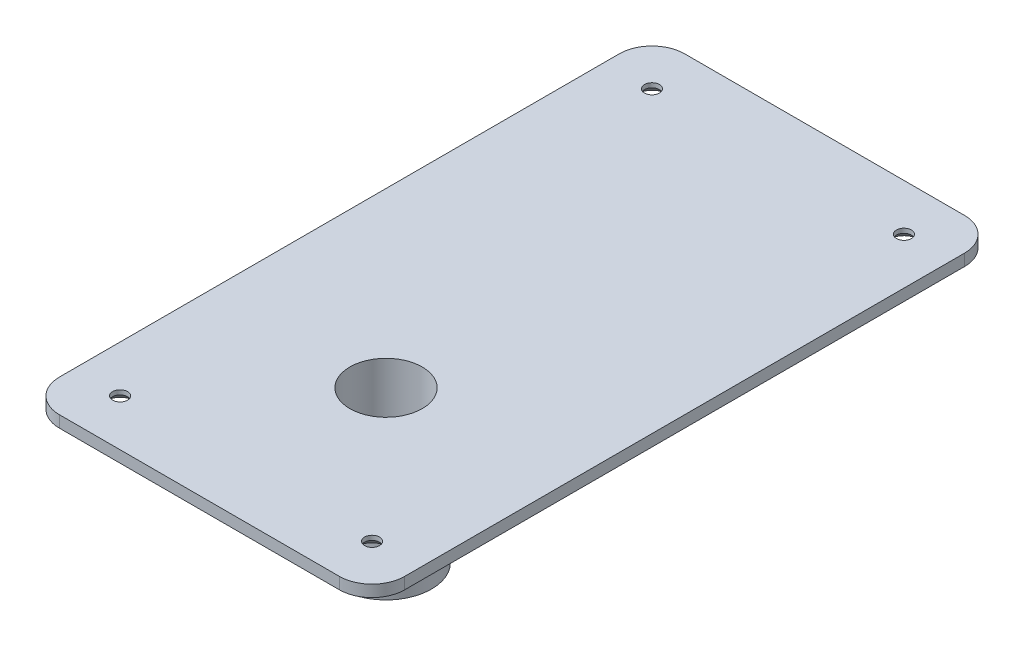
SolidWorks part; units mm, degrees
ref_plane "Front Plane" through (0, 0, 0) normal (0, 0, 1) x (1, 0, 0)
ref_plane "Top Plane" through (0, 0, 0) normal (0, 1, 0) x (1, 0, 0)
ref_plane "Right Plane" through (0, 0, 0) normal (1, 0, 0) x (0, 0, -1)
sketch "Sketch1" plane through (0, 0, 0) normal (0, 1, 0) x (1, 0, 0)
  line L0 (-37, 60) -> (-37, -60)
  line L1 (-30, 70) -> (30, 70)
  line L2 (-40, 60) -> (-40, -60)
  line L3 (-30, -70) -> (30, -70)
  line L4 (40, 60) -> (40, -60)
  line L5 (-40, 70) -> (40, -70) construction
  line L6 (-40, -70) -> (40, 70) construction
  line L7 (-30, -67) -> (30, -67)
  line L8 (37, 60) -> (37, -60)
  line L9 (-30, 67) -> (30, 67)
  line L10 (0, 70) -> (0, -70) construction
  line L11 (40, 0) -> (-40, 0) construction
  arc A0 (-40, -60) -> (-30, -70) centre (-30, -60) ccw
  arc A1 (30, -70) -> (40, -60) centre (30, -60) ccw
  arc A2 (30, 70) -> (40, 60) centre (30, 60) cw
  arc A3 (-30, 70) -> (-40, 60) centre (-30, 60) ccw
  arc A4 (-37, -60) -> (-30, -67) centre (-30, -60) ccw
  arc A5 (30, -67) -> (37, -60) centre (30, -60) ccw
  arc A6 (30, 67) -> (37, 60) centre (30, 60) cw
  arc A7 (-30, 67) -> (-37, 60) centre (-30, 60) ccw
  circle A8 centre (0, -27) radius 7.75
  circle A9 centre (0, -27) radius 9.75
  point P0 (0, 0)
  dimension "D3" = 10
  dimension "D5" = 15.5
  dimension "D6" = 40
  dimension "D1" = 80
  dimension "D2" = 140
  dimension "D4" = 3
  dimension "D7" = 2
extrude "Boss-Extrude1" add sketch "Sketch1" along normal blind 2.5 contours L0 A4 L7 A5 L8 A6 L9 A7
extrude "Boss-Extrude3" add sketch "Sketch1<4>" against normal blind 30 contours A9 | A8
sketch "Sketch1<4>" plane through (0, 0, 0) normal (0, 1, 0) x (1, 0, 0) same geometry as "Sketch1"
extrude "Cut-Extrude1" cut sketch "Sketch1<5>" along normal blind 10 contours A8 region at (0, 0, 27)
sketch "Sketch1<5>" plane through (0, 0, 0) normal (0, 1, 0) x (1, 0, 0) same geometry as "Sketch1"
hole_wizard "CSK for M3 Countersunk Flat Head Screw1" positions "Sketch5" profile "Sketch6" countersink size "M3" standard "ISO"
sketch "Sketch5" plane through (0, 0, 0) normal (0, -1, 0) x (-1, 0, 0)
  line L0 (37, 60) -> (37, -60) construction
  line L2 (30, -67) -> (-30, -67) construction
  line L3 (0, -67) -> (0, 67) construction
  line L4 (30, 67) -> (-30, 67) construction
  line L8 (-37, 60) -> (-37, -60) construction
  line L10 (-37, 0) -> (37, 0) construction
  point P0 (27, -57)
  point P39 (-27, -57)
  point P40 (-27, 57)
  point P41 (27, 57)
  dimension "D1" = 10
  dimension "D2" = 10
sketch "Sketch6" plane through (-27, 0, 57) normal (1, 0, 0) x (0, 0, -1)
  line L0 (0, 0) -> (0, 3.4614)
  line L1 (0, 3.4614) -> (1.6, 2.5)
  line L2 (1.6, 2.5) -> (1.6, 1.55)
  line L3 (1.6, 1.55) -> (3.15, 0)
  line L5 (3.15, 0) -> (0, 0)
  line L6 (-1.6, 1.55) -> (-3.15, 0) construction
  line L10 (0, 3.4614) -> (-1.6, 2.5) construction
  line L11 (0, -6.35) -> (0, 107.95) construction
  dimension "Hole Dia." = 3.2
  dimension "Hole Depth" = 2.5
  dimension "Near C'Sink Dia." = 6.3
  dimension "Near C'Sink Angle" = 90
  dimension "Drill Angle" = 118
